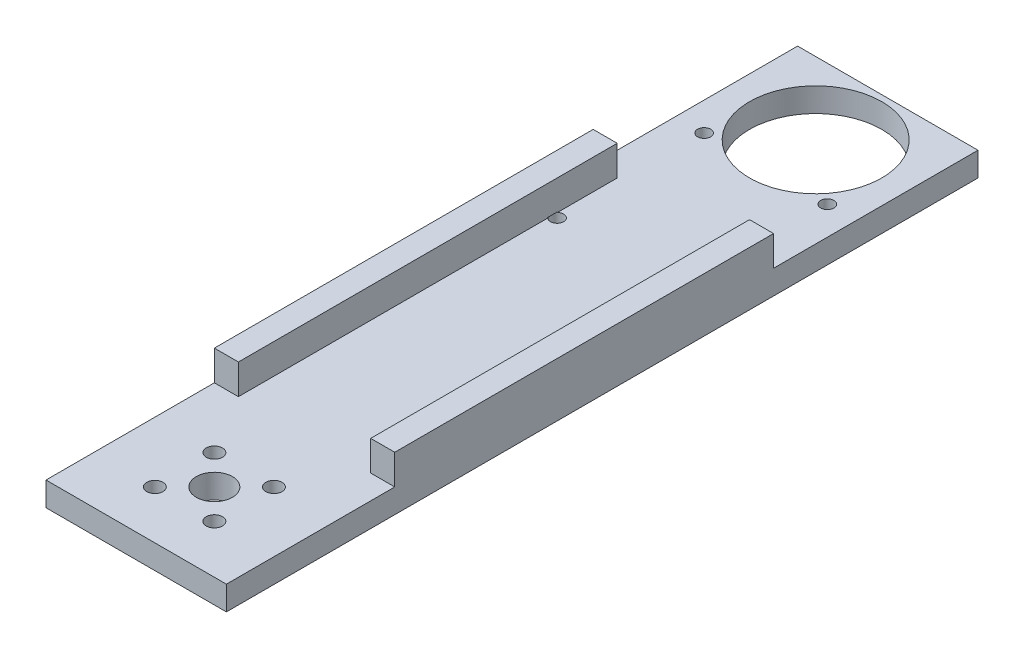
SolidWorks part; units mm, degrees
ref_plane "Front Plane" through (0, 0, 0) normal (0, 0, 1) x (1, 0, 0)
ref_plane "Top Plane" through (0, 0, 0) normal (0, 1, 0) x (1, 0, 0)
ref_plane "Right Plane" through (0, 0, 0) normal (1, 0, 0) x (0, 0, -1)
ref_plane "PZ_m112_000" through (0, 0, -112) normal (0, 0, 1) x (1, 0, 0)
sketch "S_box1" plane through (0, 0, -112) normal (0, 0, 1) x (1, 0, 0)
  line L0 (-15, 16) -> (15, 16)
  line L1 (15, 16) -> (15, 20)
  line L2 (15, 20) -> (-15, 20)
  line L3 (-15, 20) -> (-15, 16)
  dimension "P1" = 15
  dimension "P2" = 16
  dimension "P3" = 15
  dimension "P4" = 16
  dimension "P5" = 15
  dimension "P6" = 20
  dimension "P7" = 15
  dimension "P8" = 20
extrude "Boss_1" add sketch "S_box1" along normal blind 125
ref_plane "PZ_m78_000" through (0, 0, -78) normal (0, 0, 1) x (1, 0, 0)
sketch "S_box2" plane through (0, 0, -78) normal (0, 0, 1) x (1, 0, 0)
  line L0 (-15, 19.5) -> (-11, 19.5)
  line L1 (-11, 19.5) -> (-11, 25)
  line L2 (-11, 25) -> (-15, 25)
  line L3 (-15, 25) -> (-15, 19.5)
  dimension "P1" = 15
  dimension "P2" = 19.5
  dimension "P3" = 11
  dimension "P4" = 19.5
  dimension "P5" = 11
  dimension "P6" = 25
  dimension "P7" = 15
  dimension "P8" = 25
extrude "Boss_2" add sketch "S_box2" along normal blind 63
sketch "S_box3" plane through (0, 0, -78) normal (0, 0, 1) x (1, 0, 0)
  line L0 (11, 19.5) -> (15, 19.5)
  line L1 (15, 19.5) -> (15, 25)
  line L2 (15, 25) -> (11, 25)
  line L3 (11, 25) -> (11, 19.5)
  dimension "P1" = 11
  dimension "P2" = 19.5
  dimension "P3" = 15
  dimension "P4" = 19.5
  dimension "P5" = 15
  dimension "P6" = 25
  dimension "P7" = 11
  dimension "P8" = 25
extrude "Boss_3" add sketch "S_box3" along normal blind 63
ref_plane "PY_p15_900" through (0, 15.9, 0) normal (0, 1, 0) x (1, 0, 0)
sketch "S_hole4" plane through (0, 15.9, 0) normal (0, 1, 0) x (1, 0, 0)
  circle A0 centre (0, 0) radius 3
  dimension "D1_S_hole4" = 6
extrude "Hole_4" cut sketch "S_hole4" along normal blind 4.2
sketch "S_hole5" plane through (0, 15.9, 0) normal (0, 1, 0) x (1, 0, 0)
  circle A0 centre (4.9497, -4.9497) radius 1.35
  dimension "D1_S_hole5" = 2.7
  dimension "P2" = 4.9497
  dimension "P3" = 4.9497
extrude "Hole_5" cut sketch "S_hole5" along normal blind 4.2
sketch "S_hole6" plane through (0, 15.9, 0) normal (0, 1, 0) x (1, 0, 0)
  circle A0 centre (-4.9497, -4.9497) radius 1.35
  dimension "D1_S_hole6" = 2.7
  dimension "P2" = 4.9497
  dimension "P3" = 4.9497
extrude "Hole_6" cut sketch "S_hole6" along normal blind 4.2
sketch "S_hole7" plane through (0, 15.9, 0) normal (0, 1, 0) x (1, 0, 0)
  circle A0 centre (-4.9497, 4.9497) radius 1.35
  dimension "D1_S_hole7" = 2.7
  dimension "P2" = 4.9497
  dimension "P3" = 4.9497
extrude "Hole_7" cut sketch "S_hole7" along normal blind 4.2
sketch "S_hole8" plane through (0, 15.9, 0) normal (0, 1, 0) x (1, 0, 0)
  circle A0 centre (4.9497, 4.9497) radius 1.35
  dimension "D1_S_hole8" = 2.7
  dimension "P2" = 4.9497
  dimension "P3" = 4.9497
extrude "Hole_8" cut sketch "S_hole8" along normal blind 4.2
sketch "S_hole9" plane through (0, 15.9, 0) normal (0, 1, 0) x (1, 0, 0)
  circle A0 centre (0, 100) radius 11
  dimension "D1_S_hole9" = 22
  dimension "P2" = 100
extrude "Hole_9" cut sketch "S_hole9" along normal blind 4.2
sketch "S_hole10" plane through (0, 15.9, 0) normal (0, 1, 0) x (1, 0, 0)
  circle A0 centre (-10.25, 91.7) radius 1.1
  dimension "D1_S_hole10" = 2.2
  dimension "P2" = 10.25
  dimension "P3" = 91.7
extrude "Hole_10" cut sketch "S_hole10" along normal blind 4.2
sketch "S_hole11" plane through (0, 15.9, 0) normal (0, 1, 0) x (1, 0, 0)
  circle A0 centre (10.25, 91.7) radius 1.1
  dimension "D1_S_hole11" = 2.2
  dimension "P2" = 10.25
  dimension "P3" = 91.7
extrude "Hole_11" cut sketch "S_hole11" along normal blind 4.2
sketch "S_hole12" plane through (0, 15.9, 0) normal (0, 1, 0) x (1, 0, 0)
  circle A0 centre (-10.25, 67.25) radius 1.1
  dimension "D1_S_hole12" = 2.2
  dimension "P2" = 10.25
  dimension "P3" = 67.25
extrude "Hole_12" cut sketch "S_hole12" along normal blind 4.2
sketch "S_hole13" plane through (0, 15.9, 0) normal (0, 1, 0) x (1, 0, 0)
  circle A0 centre (10.25, 67.25) radius 1.1
  dimension "D1_S_hole13" = 2.2
  dimension "P2" = 10.25
  dimension "P3" = 67.25
extrude "Hole_13" cut sketch "S_hole13" along normal blind 4.2
equation "\"plate_t\" = 3"
equation "\"clearance\" = 0.4"
